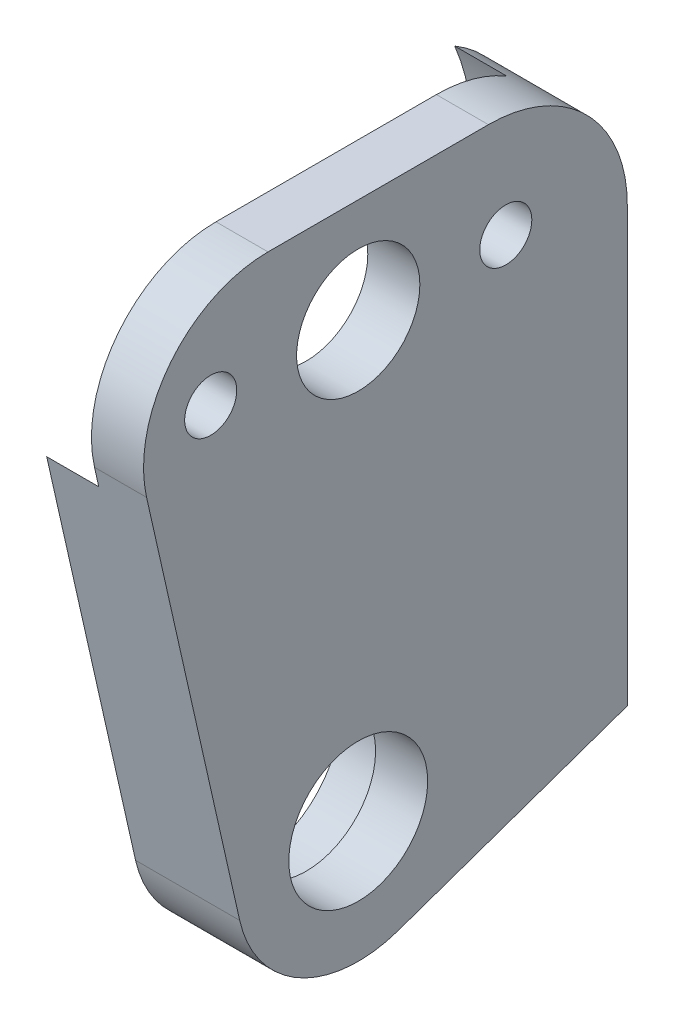
SolidWorks part; units mm, degrees
ref_plane "Front Plane" through (0, 0, 0) normal (0, 0, 1) x (1, 0, 0)
ref_plane "Top Plane" through (0, 0, 0) normal (0, 1, 0) x (1, 0, 0)
ref_plane "Right Plane" through (0, 0, 0) normal (1, 0, 0) x (0, 0, -1)
sketch "Sketch1" plane through (0, 0, 0) normal (1, 0, 0) x (0, 0, -1)
  line L0 (29.1506, 18.5) -> (16.4533, 18.5)
  line L1 (9.4569, 9.75) -> (14.8221, -14.04)
  line L2 (37.1506, 10.5) -> (37.1506, -14.5)
  line L3 (30.1506, 12.5) -> (13.1506, 12.5) construction
  line L4 (37.1506, -14.5) -> (23.9592, -19.1084)
  line L6 (-9, -42) -> (51, -42) construction
  line L7 (-9, -42) -> (-9, 16) construction
  line L8 (-9, 16) -> (51, 16) construction
  line L9 (51, -42) -> (51, 16) construction
  line L10 (37.1506, -12.5) -> (31.1506, -12.5) construction
  line L11 (37.1506, -12.5) -> (37.1506, -0.5) construction
  line L12 (37.1506, -0.5) -> (31.1506, -0.5) construction
  line L13 (31.1506, -12.5) -> (31.1506, -0.5) construction
  arc A0 (29.1506, 18.5) -> (37.1506, 10.5) centre (29.1506, 10.5) cw
  circle A1 centre (21.6506, 12.5) radius 12.5 construction
  arc A2 (16.4533, 18.5) -> (9.4569, 9.75) centre (16.4533, 11.3279) ccw
  circle A3 centre (21.6506, 12.5) radius 3.55
  circle A4 centre (21.6506, -12.5) radius 8.5 construction
  circle A5 centre (0, 0) radius 4 construction
  arc A6 (14.8221, -14.04) -> (23.9592, -19.1084) centre (21.6506, -12.5) ccw
  circle A7 centre (30.1506, 12.5) radius 1.5
  circle A8 centre (13.1506, 12.5) radius 1.5
  circle A9 centre (30.1506, 12.5) radius 3.25 construction
  circle A10 centre (13.1506, 12.5) radius 3.25 construction
  circle A12 centre (21.6506, -12.5) radius 4
  dimension "D5" = 15.5
  dimension "D6" = 8
  dimension "D7" = 7
  dimension "D8" = 25
  dimension "D10" = 7.1
  dimension "D14" = 12
  dimension "D15" = 3
  dimension "D17" = 8
  dimension "D18" = 2
  dimension "D25" = 8
  dimension "D12" = 17
  dimension "D3" = 6
  dimension "D1" = 60
  dimension "D2" = 58
  dimension "D4" = 9
  dimension "D9" = 12.5
  dimension "D11" = 25
  dimension "D13" = 6
  dimension "D16" = 8.5
  dimension "D22" = 25
  dimension "D24" = 25
extrude "Boss-Extrude1" add sketch "Sketch1" along normal blind 6
sketch "Sketch2" plane through (0, 0, 0) normal (1, 0, 0) x (0, 0, -1)
  circle A0 centre (21.6506, -12.5) radius 4.99
  dimension "D1" = 9.98
extrude "Cut-Extrude1" cut sketch "Sketch2" along normal blind 3
sketch "Sketch3" plane through (0, 0, 0) normal (1, 0, 0) x (0, 0, -1)
  circle A0 centre (21.6506, 12.5) radius 12.55
  dimension "D1" = 25.1
extrude "Cut-Extrude2" cut sketch "Sketch3" along normal blind 3
sketch "Sketch4" plane through (0, 0, 0) normal (-1, 0, 0) x (0, 0, 1)
  line L0 (-37.1506, -14.5) -> (-37.1506, 10.5) construction
  line L1 (-37.1506, -12.5) -> (-31.1506, -12.5)
  line L2 (-37.1506, -12.5) -> (-37.1506, -0.5)
  line L3 (-37.1506, -0.5) -> (-31.1506, -0.5)
  line L4 (-31.1506, -12.5) -> (-31.1506, -0.5)
  line L5 (-21.6506, -12.5) -> (-31.1506, -12.5) construction
  dimension "D1" = 6
  dimension "D2" = 12
extrude "Cut-Extrude3" cut sketch "Sketch4" against normal blind 3
